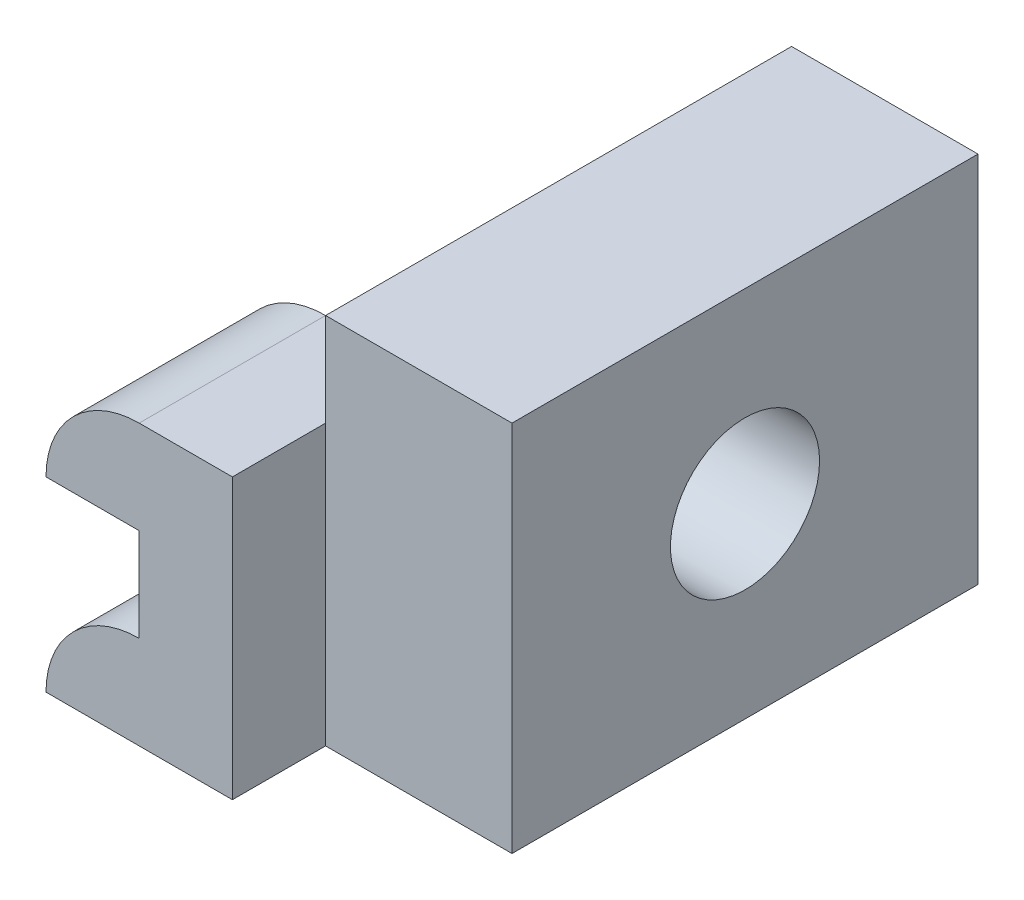
SolidWorks part; units mm, degrees
ref_plane "Front Plane" through (0, 0, 0) normal (0, 0, 1) x (1, 0, 0)
ref_plane "Top Plane" through (0, 0, 0) normal (0, 1, 0) x (1, 0, 0)
ref_plane "Right Plane" through (0, 0, 0) normal (1, 0, 0) x (0, 0, -1)
sketch "Sketch1" plane through (0, 0, 0) normal (0, 0, 1) x (1, 0, 0)
  line L0 (0, 0) -> (20, 0)
  line L1 (20, 0) -> (20, 40)
  line L2 (20, 40) -> (0, 40)
  line L3 (0, 40) -> (0, 30)
  line L4 (0, 0) -> (-20, 0)
  line L5 (-20, 0) -> (-20, 10)
  line L6 (-20, 30) -> (0, 30)
  line L7 (-20, 20) -> (-10, 20)
  line L8 (-10, 20) -> (-10, 10)
  line L9 (-10, 10) -> (-20, 10)
  line L10 (-20, 20) -> (-20, 30)
  dimension "D1" = 40
  dimension "D2" = 30
  dimension "D3" = 20
  dimension "D4" = 20
  dimension "D5" = 10
  dimension "D6" = 10
  dimension "D7" = 10
extrude "Boss-Extrude1" add sketch "Sketch1" along normal blind 60
sketch "Sketch2" plane through (-20, 0, 0) normal (-1, 0, 0) x (0, 0, 1)
  line L0 (60, 10) -> (0, 10) construction
  line L1 (0, 30) -> (40, 30)
  line L2 (0, 30) -> (0, 10)
  line L3 (0, 10) -> (40, 10)
  line L4 (40, 30) -> (40, 10)
  dimension "D1" = 20
  dimension "D2" = 40
extrude "Cut-Extrude1" cut sketch "Sketch2" against normal blind 20
fillet "Fillet1" radius 10 1 edges at (-20, 10, 30)
fillet "Fillet2" radius 10 1 edges at (-20, 30, 50)
sketch "Sketch3" plane through (0, 0, 60) normal (0, 0, 1) x (1, 0, 0)
  line L0 (-20, 0) -> (20, 0) construction
  line L1 (0, 40) -> (20, 40)
  line L2 (0, 40) -> (0, 0)
  line L3 (0, 0) -> (20, 0)
  line L4 (20, 40) -> (20, 0)
  line L5 (20, 0) -> (20, 40) construction
  dimension "D1" = 40
extrude "Cut-Extrude2" cut sketch "Sketch3" against normal blind 10
sketch "Sketch4" plane through (20, 0, 0) normal (1, 0, 0) x (0, 0, -1)
  line L0 (0, 0) -> (0, 40) construction
  line L1 (-50, 0) -> (0, 0) construction
  circle A0 centre (-25, 20) radius 8
  point P2 (-23.7298, 17.0243)
  dimension "D1" = 16
  dimension "D2" = 25
  dimension "D3" = 20
extrude "Cut-Extrude3" cut sketch "Sketch4" against normal through all
